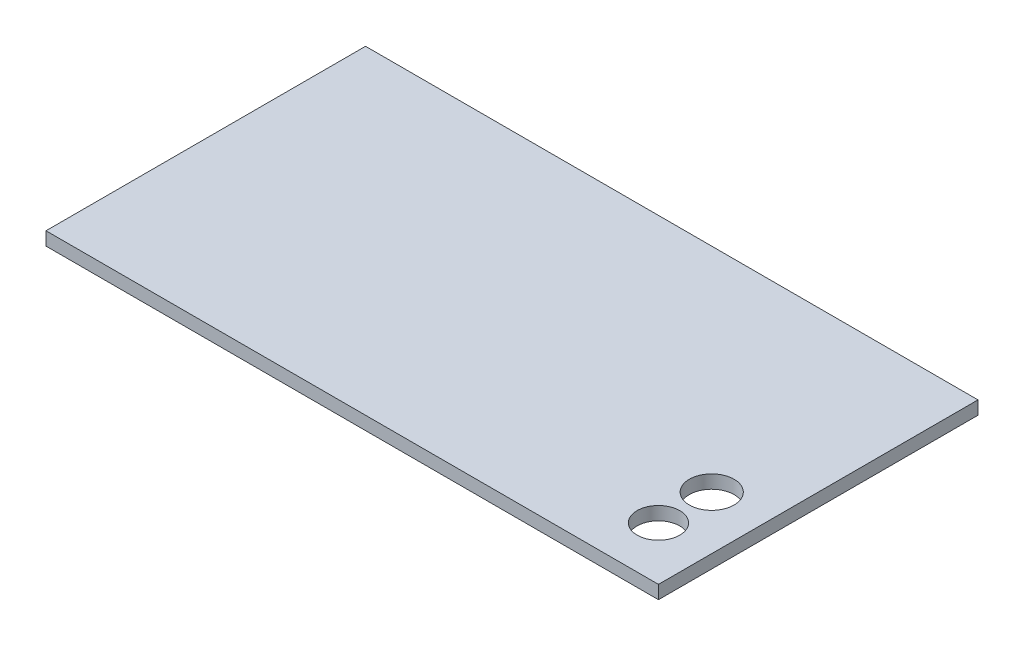
SolidWorks part; units mm, degrees
ref_plane "Front Plane" through (0, 0, 0) normal (0, 0, 1) x (1, 0, 0)
ref_plane "Top Plane" through (0, 0, 0) normal (0, 1, 0) x (1, 0, 0)
ref_plane "Right Plane" through (0, 0, 0) normal (1, 0, 0) x (0, 0, -1)
sketch "Sketch1" plane through (0, 0, 0) normal (0, 1, 0) x (1, 0, 0)
  line L1 (0, 0) -> (146.05, 0)
  line L2 (0, 0) -> (0, 76.2)
  line L3 (0, 76.2) -> (146.05, 76.2)
  line L4 (146.05, 0) -> (146.05, 76.2)
  circle A0 centre (133.35, 12.7) radius 5.08
  circle A1 centre (133.35, 25.4) radius 5.334
  dimension "D3" = 10.668
  dimension "D4" = 10.16
  dimension "D1" = 76.2
  dimension "D2" = 146.05
  dimension "D5" = 12.7
  dimension "D6" = 12.7
  dimension "D7" = 12.7
  dimension "D8" = 12.7
extrude "Boss-Extrude1" add sketch "Sketch1" along normal blind 3.175
